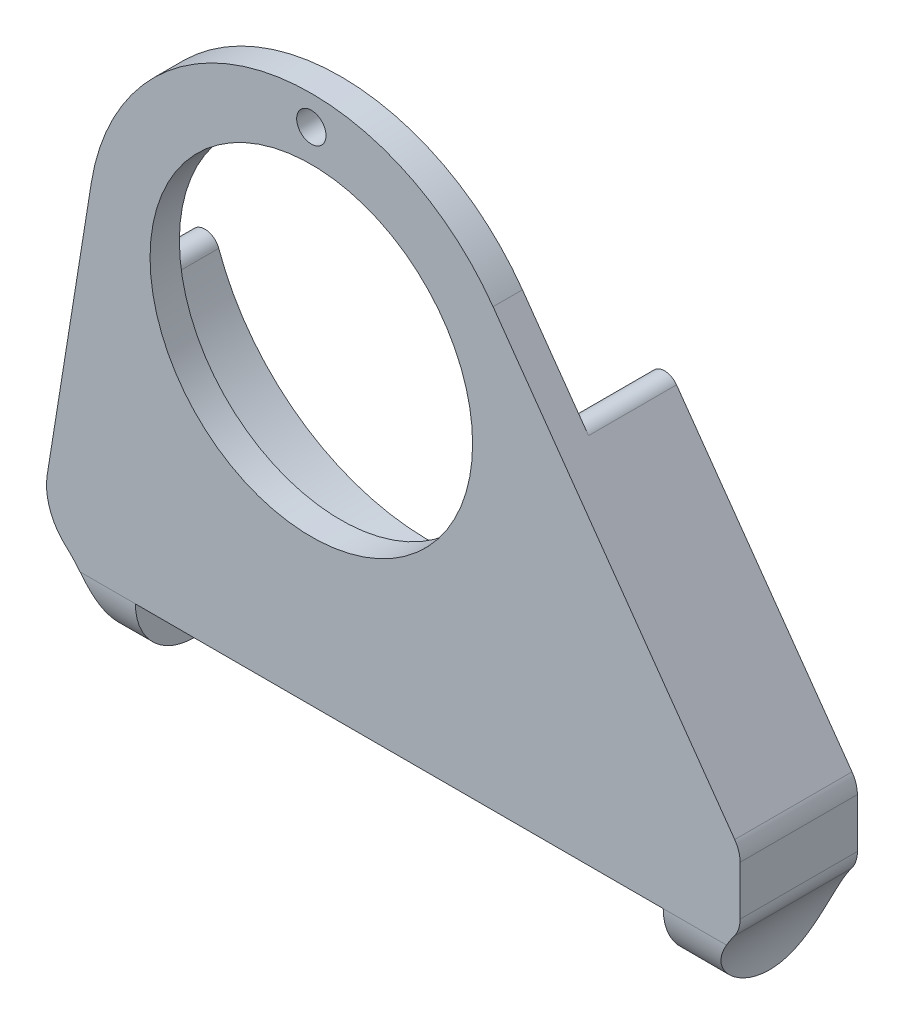
SolidWorks part; units mm, degrees
ref_plane "前视基准面" through (0, 0, 0) normal (0, 0, 1) x (1, 0, 0)
ref_plane "上视基准面" through (0, 0, 0) normal (0, 1, 0) x (1, 0, 0)
ref_plane "右视基准面" through (0, 0, 0) normal (1, 0, 0) x (0, 0, -1)
other "Configuration Table"
sketch "草图1" plane through (0, 0, 0) normal (0, 0, 1) x (1, 0, 0)
  circle A0 centre (0, 0) radius 38
  circle A1 centre (0, 0) radius 33 construction
  circle A2 centre (0, 33) radius 2.5
  circle A3 centre (0, 0) radius 27.5
  dimension "D1" = 76
  dimension "D2" = 66
  dimension "D3" = 5
  dimension "D4" = 55
extrude "凸台-拉伸1" add sketch "草图1" along normal blind 5
sketch "草图2" plane through (0, 0, 0) normal (0, 0, -1) x (-1, 0, 0)
  line L0 (-30.995, 21.9843) -> (-73.1164, -37.4014)
  line L1 (-73.1164, -37.4014) -> (-73.1164, -52.3924)
  line L2 (-73.1164, -52.3924) -> (46.8836, -52.3924)
  line L3 (46.8836, -52.3924) -> (37.521, 6.0146)
  circle A0 centre (0, 0) radius 38 construction
  arc A1 (-30.995, 21.9843) -> (37.521, 6.0146) centre (0, 0) ccw
  dimension "D1" = 120
extrude "凸台-拉伸2" add sketch "草图2" against normal blind 20
fillet "圆角2" radius 2.5 2 edges at (30.995, 21.9843, 12.5) (-37.521, 6.0146, 12.5)
fillet "圆角3" radius 10 1 edges at (-46.8836, -52.3924, 10)
fillet "圆角4" radius 5 2 edges at (73.1164, -52.3924, 10) (73.1164, -37.4014, 10)
mirror "镜向1" about plane through (0, 0, 0) normal (0, 0, 1) of "凸台-拉伸1", "圆角4", "圆角3", "圆角2", "凸台-拉伸2"
sketch "草图3" plane through (0, 0, 20) normal (0, 0, 1) x (1, 0, 0)
  line L1 (-133.1078, 81.3793) -> (133.1078, 81.3793)
  line L2 (-133.1078, 81.3793) -> (-133.1078, -81.3793)
  line L3 (-133.1078, -81.3793) -> (133.1078, -81.3793)
  line L5 (133.1078, 81.3793) -> (133.1078, -81.3793)
  line L6 (-133.1078, 81.3793) -> (133.1078, -81.3793) construction
  line L7 (-133.1078, -81.3793) -> (133.1078, 81.3793) construction
  point P0 (0, 0)
extrude "切除-拉伸1" cut sketch "草图3" against normal blind 20
sketch "草图5" plane through (0, -52.3924, 0) normal (0, -1, 0) x (1, 0, 0)
  line L0 (68.1164, -20) -> (68.1164, 0) construction
  line L1 (-35.153, 0) -> (68.1164, 0)
  line L2 (-35.153, 0) -> (-35.153, -10)
  line L3 (-35.153, -10) -> (68.1164, -10)
  line L4 (68.1164, 0) -> (68.1164, -10)
revolve "旋转1" add sketch "草图5" angle 180 about L3
fillet "圆角5" radius 20 2 edges at (68.1164, -52.3924, -10) (-35.153, -52.3924, -10)
ref_plane "基准面1" through (0, 0, -10) normal (0, 0, 1) x (1, 0, 0)
sketch "草图6" plane through (0, 0, 0) normal (1, 0, 0) x (0, 0, -1)
  line L0 (0, 0) -> (10, 0) construction
  line L1 (10, 0) -> (10, -52.3924) construction
  circle A0 centre (10, -52.3924) radius 10
  dimension "D1" = 20
extrude "切除-拉伸2" cut sketch "草图6" against normal blind 30 and the other way blind 60
